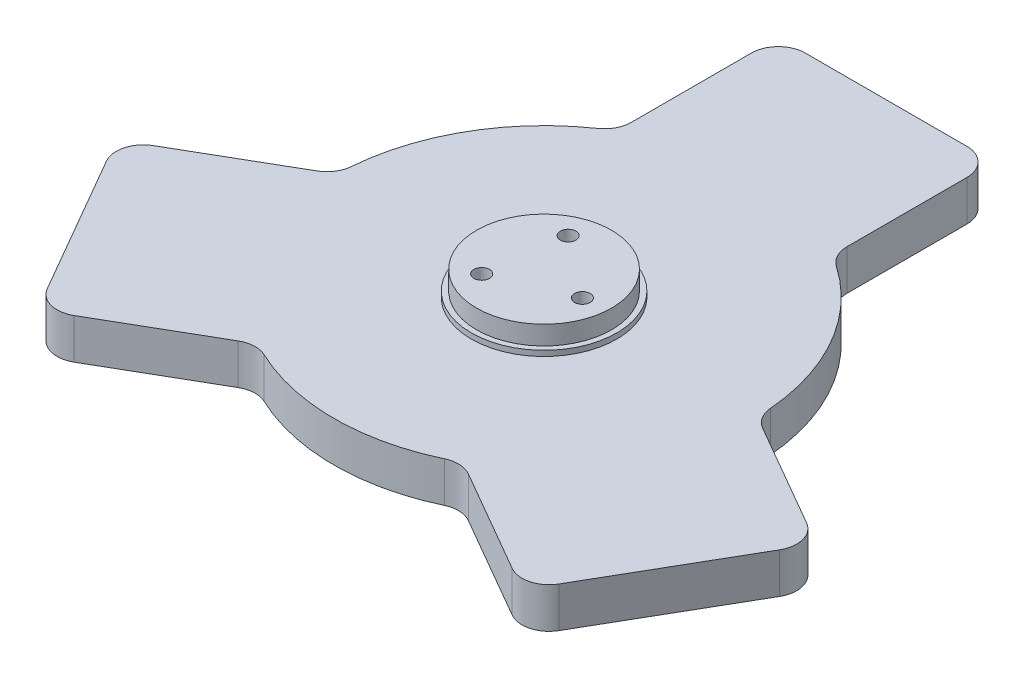
SolidWorks part; units mm, degrees
ref_plane "Front Plane" through (0, 0, 0) normal (0, 0, 1) x (1, 0, 0)
ref_plane "Top Plane" through (0, 0, 0) normal (0, 1, 0) x (1, 0, 0)
ref_plane "Right Plane" through (0, 0, 0) normal (1, 0, 0) x (0, 0, -1)
sketch "Sketch1" plane through (0, 0, 0) normal (0, 1, 0) x (1, 0, 0)
  line L0 (-40, 66.9627) -> (-40, 126.9627)
  line L1 (-40, 126.9627) -> (40, 126.9627)
  line L2 (40, 126.9627) -> (40, 66.9627)
  line L3 (89.9529, -98.1224) -> (37.9914, -68.1224)
  line L4 (129.9529, -28.8403) -> (89.9529, -98.1224)
  line L5 (77.9914, 1.1597) -> (129.9529, -28.8403)
  line L6 (-129.9529, -28.8403) -> (-77.9914, 1.1597)
  line L7 (-89.9529, -98.1224) -> (-129.9529, -28.8403)
  line L8 (-37.9914, -68.1224) -> (-89.9529, -98.1224)
  circle A0 centre (0, 0) radius 78
  arc A1 (-40, 66.9627) -> (40, 66.9627) centre (0, 0) cw
  arc A2 (77.9914, 1.1597) -> (37.9914, -68.1224) centre (0, 0) cw
  arc A3 (-37.9914, -68.1224) -> (-77.9914, 1.1597) centre (0, 0) cw
  point P5 (0, 126.9627)
  point P20 (0, 0)
  dimension "D1" = 156
  dimension "D2" = 80
  dimension "D3" = 60
  dimension "D4" = 3
extrude "Boss-Extrude1" add sketch "Sketch1" along normal blind 15 contours A0 L2 L1 L0 | A0 | L6 A3 L8 L7 | L3 A2 L5 L4 region at (0, 0, -100.5965) region at (0, 0, 0)
sketch "Sketch2" plane through (0, 15, 0) normal (0, 1, 0) x (1, 0, 0)
  circle A0 centre (0, 0) radius 27
  dimension "D1" = 54
extrude "Boss-Extrude2" add sketch "Sketch2" along normal blind 2
sketch "Sketch3" plane through (0, 17, 0) normal (0, 1, 0) x (1, 0, 0)
  circle A0 centre (0, 0) radius 25.05
  dimension "D1" = 50.1
extrude "Boss-Extrude3" add sketch "Sketch3" along normal blind 7
sketch "Sketch6" plane through (0, 0, 0) normal (0, -1, 0) x (-1, 0, 0)
  line L0 (6.3181, 15.2533) -> (0, 0) construction
  line L1 (0, 0) -> (10.0507, -13.0983) construction
  line L3 (0, 0) -> (-16.3688, -2.155) construction
  line L4 (0, 0) -> (0, -64.4806) construction
  point P0 (-16.3688, -2.155)
  point P2 (6.3181, 15.2533)
  point P4 (10.0507, -13.0983)
  dimension "D1" = 16.51
  dimension "D2" = 82.5
  dimension "D3" = 120
  dimension "D4" = 120
hole_wizard "CBORE for M5 SHCS1" positions "Sketch6" profile "Sketch5" counterbore size "M5" standard "ANSI Metric" end condition through all
sketch "Sketch5" plane through (16.3688, 0, 2.155) normal (1, 0, 0) x (0, 0, -1)
  line L0 (0, 0) -> (0, 24)
  line L1 (0, 24) -> (2.9, 24)
  line L3 (2.9, 24) -> (2.9, 5)
  line L4 (5, 5) -> (2.9, 5)
  line L5 (5, 5) -> (5, 0.025)
  line L6 (5, 0.025) -> (5.025, 0)
  line L7 (5.025, 0) -> (0, 0)
  line L8 (-5, 0.025) -> (-5.025, 0) construction
  line L11 (0, -6.35) -> (0, 107.95) construction
  dimension "Thru Hole Dia." = 5.8
  dimension "Thru Hole Depth" = 24
  dimension "C'Bore Dia." = 10
  dimension "C'Bore Depth" = 5
  dimension "Near C'Sink Dia." = 10.05
  dimension "Near C'Sink Angle" = 90
fillet "Fillet1" radius 10 12 edges at (40, 7.5, -66.9627) (-40, 7.5, -66.9627) (40, 7.5, -126.9627) (-40, 7.5, -126.9627) (77.9914, 7.5, -1.1597) (129.9529, 7.5, 28.8403) (89.9529, 7.5, 98.1224) (37.9914, 7.5, 68.1224) (-37.9914, 7.5, 68.1224) (-89.9529, 7.5, 98.1224) (-129.9529, 7.5, 28.8403) (-77.9914, 7.5, -1.1597)
ref_axis "Axis1" through (0, 107.4683, 0) along (0, -1, 0)
